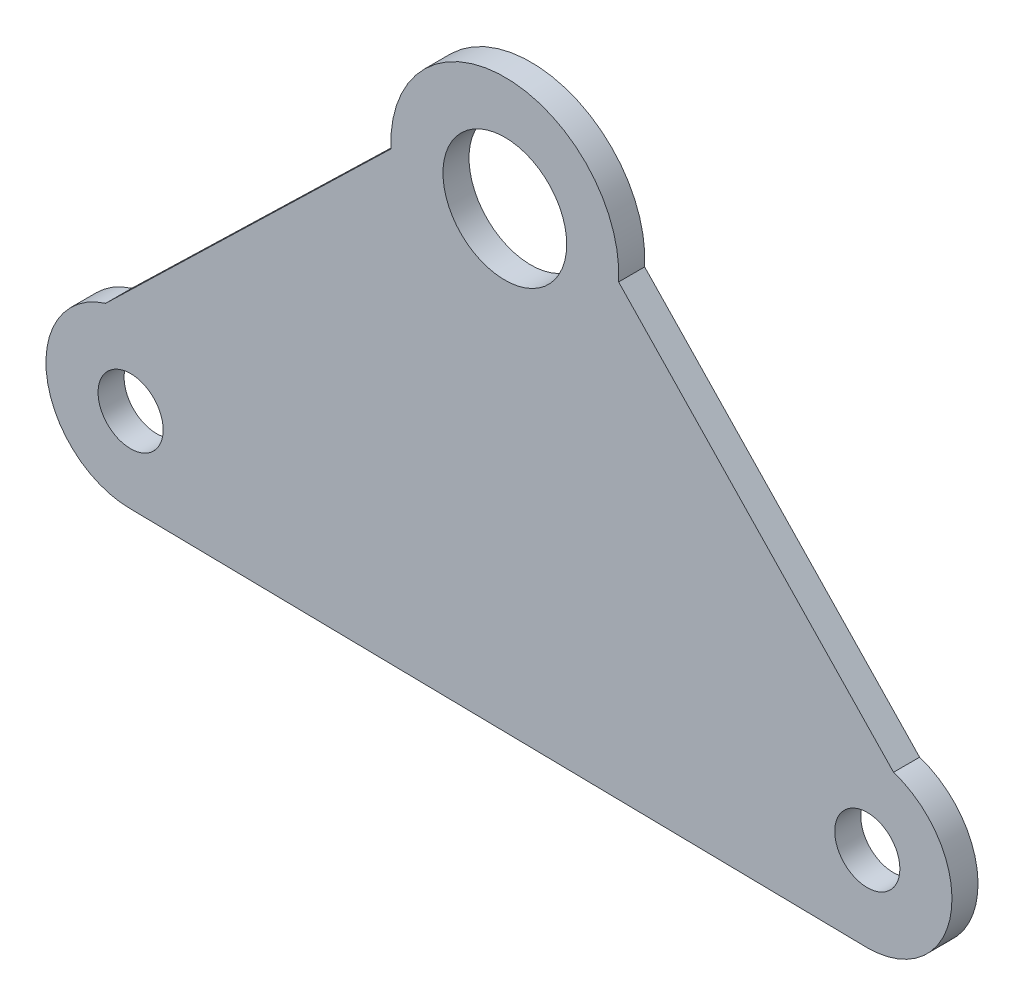
SolidWorks part; units mm, degrees
ref_plane "前视基准面" through (0, 0, 0) normal (0, 0, 1) x (1, 0, 0)
ref_plane "上视基准面" through (0, 0, 0) normal (0, 1, 0) x (1, 0, 0)
ref_plane "右视基准面" through (0, 0, 0) normal (1, 0, 0) x (0, 0, -1)
sketch "草图1" plane through (0, 0, 0) normal (0, 0, 1) x (1, 0, 0)
  line L0 (0, 0) -> (-57.463, -55.6597) construction
  line L1 (-57.463, -55.6597) -> (55.6597, -57.463) construction
  line L2 (55.6597, -57.463) -> (0, 0) construction
  line L3 (-57.463, -50.6597) -> (-8.816, -3.5394) construction
  line L4 (55.6597, -52.463) -> (8.816, -3.5394)
  line L5 (-57.463, -60.6597) -> (55.6597, -62.463) construction
  line L6 (-61.3002, -43.239) -> (-17.4819, -0.7957)
  line L7 (59.6885, -45.103) -> (17.4708, -1.0108)
  line L8 (-57.5417, -68.6595) -> (55.581, -70.4627)
  circle A0 centre (0, 0) radius 9.5
  circle A1 centre (-57.463, -55.6597) radius 5
  circle A2 centre (55.6597, -57.463) radius 5
  arc A3 (-8.816, -3.5394) -> (8.816, -3.5394) centre (0, 0) cw construction
  arc A4 (-57.463, -50.6597) -> (-57.463, -60.6597) centre (-57.463, -55.6597) ccw construction
  arc A5 (55.6597, -62.463) -> (55.6597, -52.463) centre (55.6597, -57.463) ccw construction
  arc A6 (-17.4819, -0.7957) -> (17.4708, -1.0108) centre (0, 0) cw
  arc A7 (55.581, -70.4627) -> (59.6885, -45.103) centre (55.6597, -57.463) ccw
  arc A8 (-61.3002, -43.239) -> (-57.5417, -68.6595) centre (-57.463, -55.6597) ccw
  dimension "D3" = 19
  dimension "D4" = 10
  dimension "D1" = 80
  dimension "D2" = 45
  dimension "D5" = 8
extrude "凸台-拉伸1" add sketch "草图1" along normal blind 4 contours L6 A8 L8 A7 L7 A6 A2 A0 A1 region at (-0.6136, -39.4752, 0)
